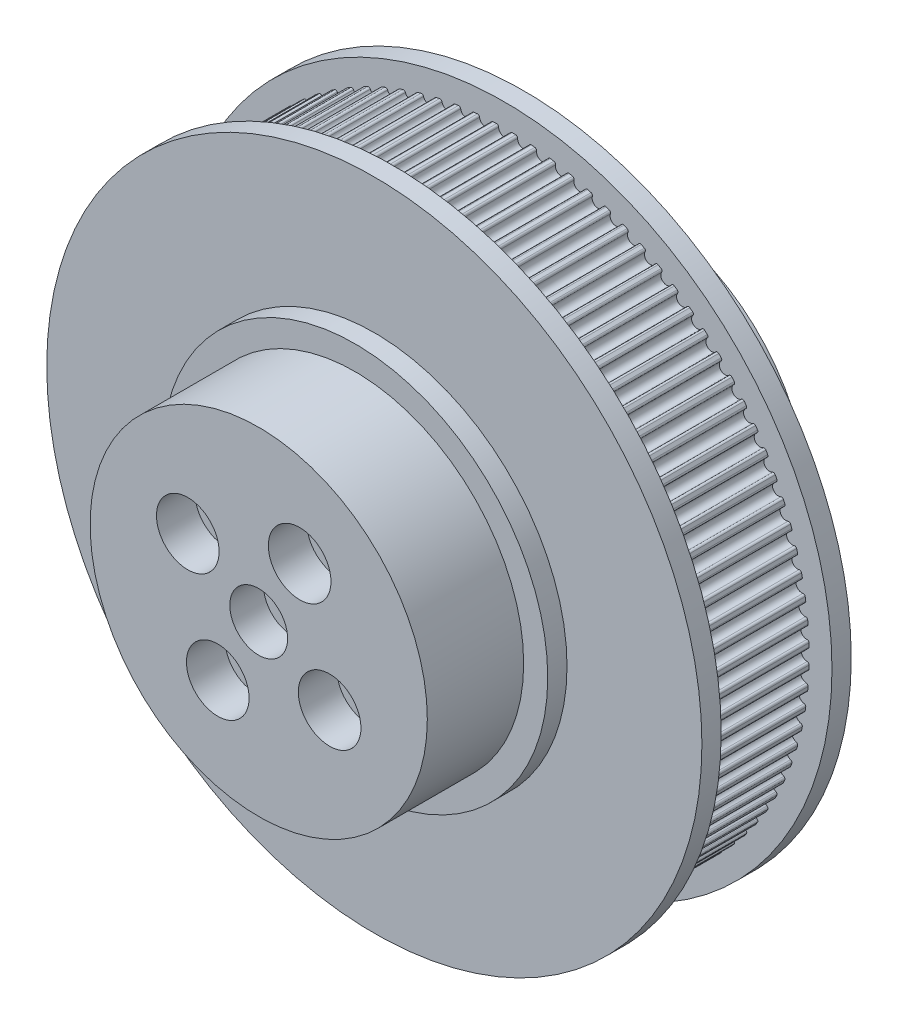
SolidWorks part; units mm, degrees
ref_plane "Спереди" through (0, 0, 0) normal (0, 0, 1) x (1, 0, 0)
ref_plane "Сверху" through (0, 0, 0) normal (0, 1, 0) x (1, 0, 0)
ref_plane "Справа" through (0, 0, 0) normal (1, 0, 0) x (0, 0, -1)
ref_axis "Ось1" through (0, 0, 55) along (0, 0, -1)
sketch "SketchRevolveGearBelt01" plane through (0, 0, 0) normal (1, 0, 0) x (0, 0, -1)
  line L0 (0, 0) -> (11.5, 0)
  line L1 (11.5, 0) -> (11.5, 31.6405)
  line L2 (11.5, 31.6405) -> (0, 31.6405)
  line L3 (0, 31.6405) -> (0, 0)
  dimension "GearBeltOutsideDiameter" = 31.6405
  dimension "D1" = 11.5
revolve "GearBelt01" add sketch "SketchRevolveGearBelt01" angle 360 about L0
sketch "SketchToothGearBelt01" plane through (0, 0, 0) normal (0, 0, 1) x (1, 0, 0)
  line L0 (-0.814, 31.63) -> (0, 34.1805)
  line L1 (0, 34.1805) -> (0.814, 31.63)
  arc A0 (0.814, 31.63) -> (0.6, 31.4215) centre (0.8086, 31.4215) ccw
  arc A1 (0.6, 31.4215) -> (-0.6, 31.4215) centre (0, 31.4215) cw
  arc A2 (-0.6, 31.4215) -> (-0.814, 31.63) centre (-0.8086, 31.4215) ccw
  dimension "GearBeltToothR1" = 0.4172
  dimension "GearBeltToothR2" = 1.2
  dimension "GearBeltToothCapX1" = 0.814
  dimension "GearBeltToothCapY1" = 2.5505
  dimension "GearBeltToothCapX2" = 0.814
  dimension "GearBeltToothCapY2" = 2.5505
extrude "ToothExtrudeCutGearBelt01" cut sketch "SketchToothGearBelt01" against normal blind 11.5
ref_axis "Ось2" through (34.8045, 0, 0) along (-1, 0, 0)
ref_plane "Плоскость1" through (0, 0, 0) normal (0, 0, -1) x (1, 0, 0)
pattern_circular "PatternGearBelt01" count 100 every 3.6 about axis through (0, 0, 55) along (0, 0, -1) of "ToothExtrudeCutGearBelt01"
sketch "Эскиз5" plane through (0, 0, 0) normal (0, 0, -1) x (-1, 0, 0)
  circle A0 centre (0, 0) radius 34
  dimension "D1" = 68
extrude "Бобышка-Вытянуть1" add sketch "Эскиз5" against normal blind 2
sketch "Эскиз20" plane through (0, 0, -11.5) normal (0, 0, -1) x (-1, 0, 0)
  circle A0 centre (0, 0) radius 34
extrude "Бобышка-Вытянуть10" add sketch "Эскиз20" along normal blind 2
sketch "Эскиз12" plane through (0, 0, -13.5) normal (0, 0, -1) x (-1, 0, 0)
  circle A0 centre (0, 0) radius 20
extrude "Бобышка-Вытянуть5" add sketch "Эскиз12" along normal blind 2
sketch "Эскиз6" plane through (0, 0, 2) normal (0, 0, 1) x (1, 0, 0)
  circle A0 centre (0, 0) radius 20
  dimension "D1" = 40
extrude "Бобышка-Вытянуть6" add sketch "Эскиз6" along normal blind 2
sketch "Эскиз13" plane through (0, 0, 4) normal (0, 0, 1) x (1, 0, 0)
  circle A0 centre (0, 0) radius 17.5
  dimension "D1" = 35
extrude "Бобышка-Вытянуть7" add sketch "Эскиз13" along normal blind 10
sketch "Эскиз14" plane through (0, 0, -15.5) normal (0, 0, -1) x (-1, 0, 0)
  circle A0 centre (0, 0) radius 17.5
  dimension "D1" = 35
extrude "Бобышка-Вытянуть8" add sketch "Эскиз14" along normal blind 10
sketch "Эскиз15" plane through (0, 0, -25.5) normal (0, 0, -1) x (-1, 0, 0)
  circle A0 centre (0, 0) radius 12
  dimension "D1" = 24
extrude "Вырез-Вытянуть1" cut sketch "Эскиз15" against normal blind 7
sketch "Эскиз16" plane through (0, 0, 0) normal (0, 0, 1) x (1, 0, 0)
  line L0 (0, 0) -> (4.25, 7.3612) construction
  line L1 (0, 0) -> (-46.2056, 0) construction
  line L2 (0, 0) -> (7.3612, -4.25) construction
  line L3 (0, 0) -> (-4.25, -7.3612) construction
  line L4 (0, 0) -> (-7.3612, 4.25) construction
  circle A0 centre (0, 0) radius 8.5 construction
  circle A1 centre (4.25, 7.3612) radius 1.75
  circle A2 centre (7.3612, -4.25) radius 1.75
  circle A3 centre (-4.25, -7.3612) radius 1.75
  circle A4 centre (-7.3612, 4.25) radius 1.75
  point P16 (0, 0)
  dimension "D1" = 17
  dimension "D3" = 3.5
  dimension "D2" = 60
  dimension "D4" = 4
extrude "Вырез-Вытянуть2" cut sketch "Эскиз16" against normal through all both and the other way through all
sketch "Эскиз17" plane through (0, 0, 14) normal (0, 0, 1) x (1, 0, 0)
  circle A0 centre (4.25, 7.3612) radius 3.25
  circle A1 centre (7.3612, -4.25) radius 3.25
  circle A2 centre (-4.25, -7.3612) radius 3.25
  circle A3 centre (-7.3612, 4.25) radius 3.25
  point P12 (0, 0)
  dimension "D1" = 4
extrude "Вырез-Вытянуть3" cut sketch "Эскиз17" against normal blind 4
sketch "Эскиз18" plane through (0, 0, 14) normal (0, 0, 1) x (1, 0, 0)
  circle A0 centre (0, 0) radius 3
extrude "Вырез-Вытянуть4" cut sketch "Эскиз18" against normal blind 3.5
sketch "Эскиз19" plane through (0, 0, 0) normal (0, 0, 1) x (1, 0, 0)
  circle A0 centre (0, 0) radius 1
extrude "Вырез-Вытянуть5" cut sketch "Эскиз19" against normal through all both and the other way through all
